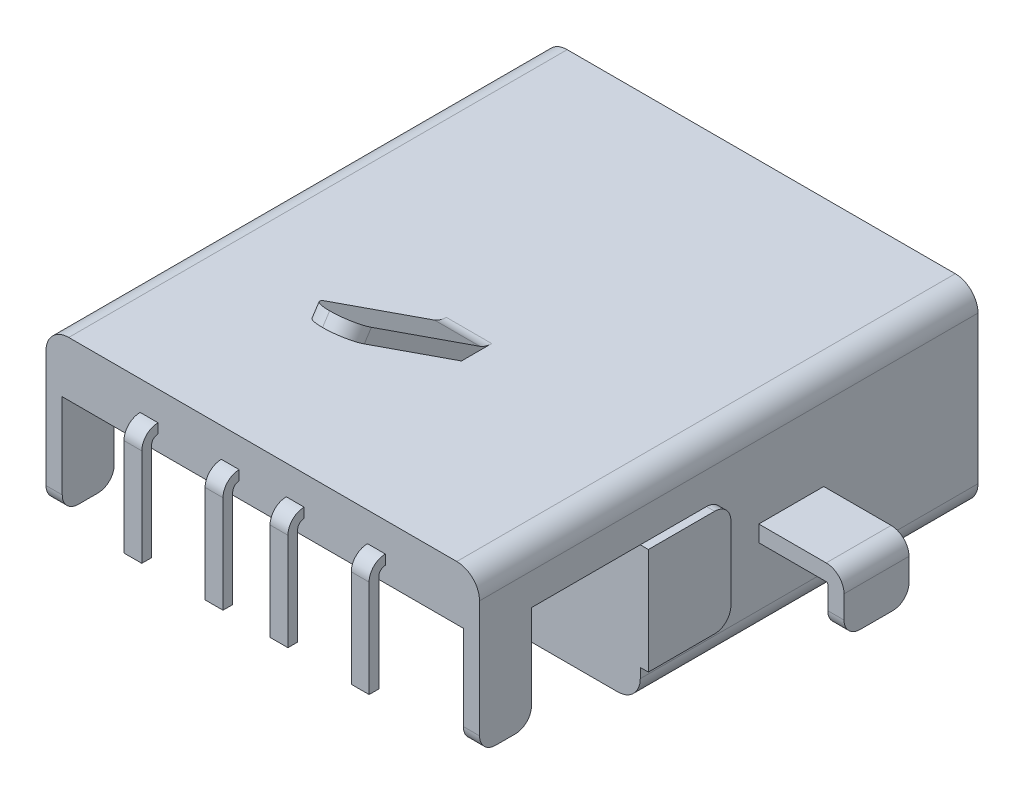
SolidWorks part; units mm, degrees
ref_plane "Ebene vorne" through (0, 0, 0) normal (0, 0, 1) x (1, 0, 0)
ref_plane "Ebene oben" through (0, 0, 0) normal (0, 1, 0) x (1, 0, 0)
ref_plane "Ebene rechts" through (0, 0, 0) normal (1, 0, 0) x (0, 0, -1)
sketch "Skizze1" plane through (0, 0, 0) normal (0, 0, 1) x (1, 0, 0)
  line L0 (-6.675, -1.68) -> (0, -1.68)
  line L1 (-6.675, 0) -> (0, 0)
  line L2 (-6.675, 0) -> (-6.675, -5.95)
  line L3 (-6.675, -5.95) -> (0, -5.95)
  line L4 (0, 0) -> (0, -5.95)
  dimension "D1" = 6.675
  dimension "D2" = 5.95
  dimension "D3" = 1.68
extrude "Aufsatz-Linear austragen1" add sketch "Skizze1" along normal blind 10.4 contours L4 L0 L2 L3 region at (-3.3375, -3.815, 0)
extrude "Aufsatz-Linear austragen2" add sketch "Skizze1<3>" along normal blind 15.35 contours L4 L1 L2 L0 region at (-3.3375, -0.84, 0)
sketch "Skizze1<3>" plane through (0, 0, 0) normal (0, 0, 1) x (1, 0, 0) same geometry as "Skizze1"
sketch "Skizze2" plane through (0, 0, 0) normal (0, 0, 1) x (1, 0, 0)
  line L0 (0, -3.2) -> (-8.75, -3.2)
  line L1 (-9.05, -3.5) -> (-9.05, -4.7)
  arc A0 (-9.05, -3.5) -> (-8.75, -3.2) centre (-8.75, -3.5) cw
  dimension "D1" = 9.05
  dimension "D3" = 0.3
  dimension "D4" = 4.7
  dimension "D2" = 3.2
extrude "Linear-Austragen-Dünn1" add sketch "Skizze2" along normal blind 2 from offset 4.75 thin thin type mid plane wall 0.5
sketch "Skizze3" plane through (0, 0, 0) normal (0, 1, 0) x (1, 0, 0)
  line L1 (-6.675, -15.35) -> (-6.175, -15.35)
  line L2 (-6.675, -15.35) -> (-6.675, -13.75)
  line L3 (-6.675, -13.75) -> (-6.175, -13.75)
  line L4 (-6.175, -15.35) -> (-6.175, -13.75)
  dimension "D1" = 0.5
  dimension "D2" = 1.6
extrude "Aufsatz-Linear austragen3" add sketch "Skizze3" against normal blind 4.8
sketch "Skizze4" plane through (0, 0, 0) normal (0, 0, 1) x (1, 0, 0)
  line L1 (1.1572, -0.5) -> (-6.18, -0.5)
  line L2 (1.1572, -0.5) -> (1.1572, -5.45)
  line L3 (1.1572, -5.45) -> (-6.18, -5.45)
  line L4 (-6.18, -0.5) -> (-6.18, -5.45)
  dimension "D1" = 0.5
  dimension "D2" = 6.18
  dimension "D3" = 5.45
extrude "Schnitt-Linear austragen1" cut sketch "Skizze4" along normal blind 8.85
sketch "Skizze5" plane through (0, 0, 0) normal (0, 0, 1) x (1, 0, 0)
  line L0 (0, -5.45) -> (0, -0.5) construction
  line L1 (0, -0.9) -> (-5.4, -0.9)
  line L2 (0, -0.9) -> (0, -2.9)
  line L3 (0, -2.9) -> (-5.4, -2.9)
  line L4 (-5.4, -0.9) -> (-5.4, -2.9)
  dimension "D1" = 2
  dimension "D2" = 5.4
  dimension "D3" = 0.9
extrude "Aufsatz-Linear austragen4" add sketch "Skizze5" along normal up to next from offset 0.5
sketch "Skizze6" plane through (0, 0, 0) normal (0, 1, 0) x (1, 0, 0)
  line L0 (-1.275, -15.85) -> (-0.725, -15.85)
  line L1 (-3.775, -15.85) -> (-3.225, -15.85)
  line L2 (-3.775, -15.85) -> (-3.775, -15.55)
  line L3 (-3.775, -15.55) -> (-3.225, -15.55)
  line L4 (-3.225, -15.85) -> (-3.225, -15.55)
  line L5 (-1.275, -15.85) -> (-1.275, -15.55)
  line L6 (-1.275, -15.55) -> (-0.725, -15.55)
  line L7 (-0.725, -15.85) -> (-0.725, -15.55)
  line L8 (-3.775, -15.55) -> (-3.775, -15.35)
  line L9 (-6.175, -15.35) -> (0, -15.35) construction
  line L10 (-3.775, -15.35) -> (-3.225, -15.35)
  line L11 (-3.225, -15.35) -> (-3.225, -15.55)
  line L12 (-1.275, -15.55) -> (-1.275, -15.35)
  line L13 (-1.275, -15.35) -> (-0.725, -15.35)
  line L14 (-0.725, -15.35) -> (-0.725, -15.55)
  point P4 (-3.5, -15.85)
  point P5 (-1, -15.85)
  dimension "D1" = 0.3
  dimension "D2" = 0.55
  dimension "D3" = 15.85
  dimension "D4" = 3.5
  dimension "D6" = 2.5
  dimension "D5" = 2
extrude "Aufsatz-Linear austragen5" add sketch "Skizze6" against normal blind 3.5 from offset 0.9 separate body contours L0 L7 L6 L5 | L1 L4 L3 L2 region at (-1, 0, 15.7) region at (-3.5, 0, 15.7) offset against normal yes
extrude "Aufsatz-Linear austragen6" add sketch "Skizze6<3>" against normal blind 0.3 from offset 0.9 contours L11 L10 L8 L3 | L14 L13 L12 L6 region at (-1, 0, 15.45) region at (-3.5, 0, 15.45) offset against normal yes
sketch "Skizze6<3>" plane through (0, 0, 0) normal (0, 1, 0) x (1, 0, 0) same geometry as "Skizze6"
fillet "Verrundung1" radius 0.2 2 edges at (-3.5, -1.2, 15.55) (-1, -1.2, 15.55)
fillet "Verrundung2" radius 0.5 2 edges at (-1, -0.9, 15.85) (-3.5, -0.9, 15.85)
fillet "Verrundung3" radius 0.3 2 edges at (-6.18, -0.5, 4.425) (-6.18, -5.45, 4.425)
fillet "Verrundung4" radius 0.7 2 edges at (-6.675, -5.95, 5.2) (-6.675, 0, 7.675)
sketch "Skizze7" plane through (0, 0, 0) normal (1, 0, 0) x (0, 0, -1)
  line L0 (-10.4, -1.68) -> (-10.4, -5.25) construction
  line L1 (-7.86, -1.68) -> (-10.4, -1.68)
  line L2 (-7.86, -1.68) -> (-7.86, -4.95)
  line L3 (-7.86, -4.95) -> (-10.4, -4.95)
  line L4 (-10.4, -1.68) -> (-10.4, -4.95)
  line L5 (-10.4, -5.95) -> (0, -5.95) construction
  dimension "D1" = 2.54
  dimension "D2" = 1
extrude "Aufsatz-Linear austragen7" add sketch "Skizze7" against normal blind 0.25 from surface starting at face at (-6.675, -3.2, 5.75)
fillet "Verrundung6" radius 0.5 4 edges at (-9.05, -4.7, 4.75) (-9.05, -4.7, 6.75) (-6.425, -4.8, 15.35) (-6.425, -4.8, 13.75)
fillet "Verrundung7" radius 0.5 2 edges at (-6.8, -4.95, 7.86) (-6.8, -1.68, 7.86)
mirror "Spiegeln1" about plane through (0, 0, 0) normal (1, 0, 0) of bodies 111 106
sketch "Skizze8" plane through (0, 0, 0) normal (1, 0, 0) x (0, 0, -1)
  line L0 (-7.1273, -0.2) -> (-9, -0.2)
  line L2 (-9.4729, -0.0595) -> (-13.4, 2.5)
  arc A0 (-9, -0.2) -> (-9.4729, -0.0595) centre (-9, 0.666) cw
  dimension "D1" = 13.4
  dimension "D4" = 0.2
  dimension "D2" = 9
  dimension "D3" = 2.5
extrude "Linear-Austragen-Dünn2" add sketch "Skizze8" along normal mid plane 1.4 thin thin type mid plane wall 0.4
fillet "Verrundung5" radius 0.7 2 edges at (-0.7, 2.5, 13.4) (0.7, 2.5, 13.4)
